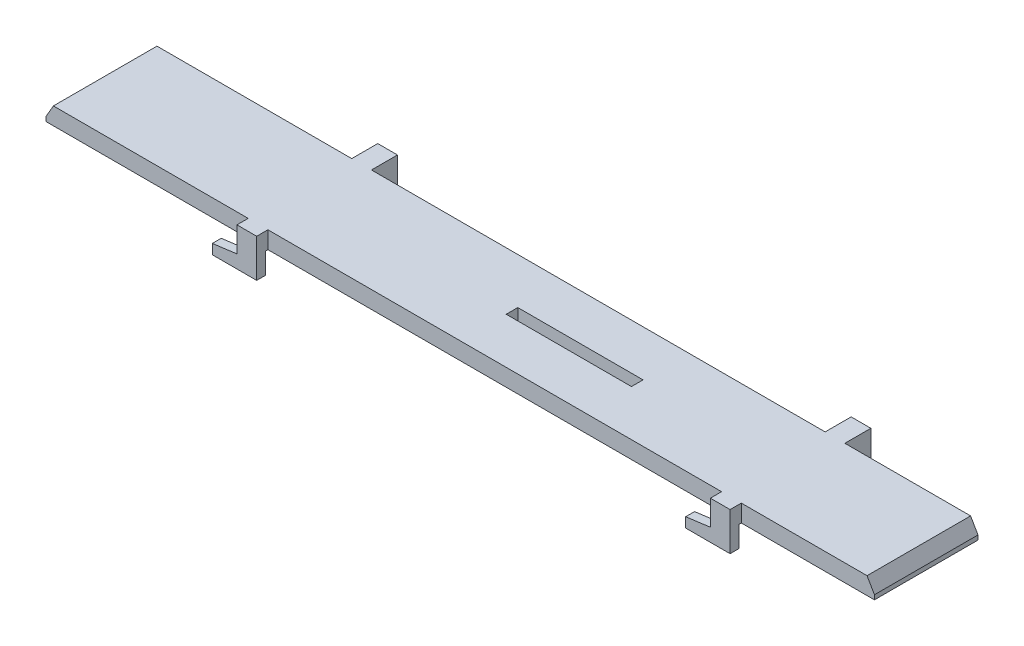
SolidWorks part; units mm, degrees
note: The reader was unsure of these and kept them because the rebuilt part matched: shared geometry of "Hook Sketch<2>".
ref_plane "Top" through (0, 0, 0) normal (0, 0, 1) x (1, 0, 0)
ref_plane "Front" through (0, 0, 0) normal (0, 1, 0) x (1, 0, 0)
ref_plane "Right" through (0, 0, 0) normal (1, 0, 0) x (0, 0, -1)
sketch "Top Sketch" plane through (0, 0, 0) normal (0, 1, 0) x (1, 0, 0)
  line L0 (-27, -11) -> (-27, -12.375)
  line L1 (-168, 10) -> (-127, 10)
  line L2 (-168, 10) -> (-168, -11)
  line L3 (-168, -11) -> (-127, -11)
  line L4 (0, 10) -> (0, -11)
  line L5 (-27, -12.375) -> (-36, -12.375) construction
  line L6 (-36, -12.375) -> (-36, -11) construction
  line L7 (-123, -11) -> (-123, -12.375)
  line L8 (-123, -12.375) -> (-132, -12.375) construction
  line L9 (-132, -12.375) -> (-132, -11) construction
  line L10 (-27, 10) -> (-27, 14.375)
  line L11 (-27, 14.375) -> (-36, 14.375) construction
  line L12 (-36, 14.375) -> (-36, 10) construction
  line L13 (-123, 10) -> (-123, 14.375)
  line L14 (-123, 14.375) -> (-132, 14.375) construction
  line L15 (-132, 14.375) -> (-132, 10) construction
  line L16 (-27, 10) -> (0, 10)
  line L17 (-27, -11) -> (0, -11)
  line L18 (-123, 10) -> (-31, 10)
  line L19 (-123, -11) -> (-31, -11)
  line L20 (-31, 14.375) -> (-31, 10)
  line L21 (-31, 14.375) -> (-27, 14.375)
  line L22 (-31, -11) -> (-31, -12.375)
  line L23 (-31, -12.375) -> (-27, -12.375)
  line L24 (-127, 14.375) -> (-127, 10)
  line L25 (-127, 14.375) -> (-123, 14.375)
  line L26 (-127, -12.375) -> (-127, -11)
  line L27 (-127, -12.375) -> (-123, -12.375)
  line L28 (-168, 0) -> (0, 0) construction
  point P32 (-84, 0)
  point P37 (0, -0.5)
  dimension "D1" = 4.375
  dimension "Width" = 21
  dimension "D2" = 1.375
  dimension "Length" = 168
  dimension "D3" = 0.5
  dimension "D5" = 5
  dimension "D8" = 4
extrude "Thickness Extrude" add sketch "Top Sketch" along normal blind 3.5
sketch "Hook Sketch" plane through (0, 0, 12.375) normal (0, 0, 1) x (1, 0, 0)
  line L0 (-31, 3.5) -> (-27, 3.5)
  line L1 (-31, 0) -> (-27, 0) construction
  line L2 (-27, 3.5) -> (-27, -4.2583)
  line L3 (-27, -4.2583) -> (-36, -4.2583)
  line L4 (-36, -4.2583) -> (-36, -2.2583)
  line L5 (-36, -2.2583) -> (-31, -1.6)
  line L6 (-31, -1.6) -> (-31, 3.5)
  dimension "D1" = 7.5
  dimension "D2" = 5
  dimension "D3" = 1.6
  dimension "D4" = 2
extrude "Hook 1 Extrude" add sketch "Hook Sketch" against normal blind 0.9 and the other way blind 0.9 separate body
extrude "Hook 2 Extrude" add sketch "Hook Sketch<2>" along normal blind 0.9 and the other way blind 0.9 from surface at -26.75 separate body
sketch "Hook Sketch<2>" plane through (0, 0, 12.375) normal (0, 0, 1) x (1, 0, 0) same geometry as "Hook Sketch"
pattern_linear "Hook Pattern" count 2 spacing 96 along (-1, 0, 0) of "Hook 1 Extrude", "Hook 2 Extrude"
combine bodies "Combine Bodies" operation type add bodies to combine 101 103 104 105 106
sketch "Handle Sketch" plane through (0, 3.5, 0) normal (0, 1, 0) x (1, 0, 0)
  line L1 (-168, -0.5) -> (0, -0.5) construction
  line L3 (-84, 0.675) -> (-58.6, 0.675)
  line L4 (-84, 0.675) -> (-84, -1.675)
  line L5 (-58.6, 0.675) -> (-58.6, -1.675)
  line L6 (-58.6, -1.675) -> (-84, -1.675)
  line L9 (-168, 10) -> (-168, -11) construction
  line L10 (0, -11) -> (0, 10) construction
  point P2 (-84, -0.5)
extrude "Handle Slot Cut" cut sketch "Handle Sketch" against normal blind 3
chamfer "Handle Slot Chamfer 1" distance 1.175 angle 67.5 1 edges at (-71.3, 0.5, 1.675)
chamfer "Handle Slot Chamfer 2" [suppressed] distance 1.175 angle 67.5
chamfer "End Chamfers" distance 2.6 angle 30 2 edges at (0, 3.5, 0.5) (-168, 3.5, 0.5)
equation "\"Handle Opening Width\"= 2.35"
equation "\"D1@Handle Sketch\"=\"Handle Opening Width\""
equation "\"D1@Handle Slot Chamfer 1\" = \"Handle Opening Width\" / 2"
equation "\"D1@Handle Slot Chamfer 2\" = \"Handle Opening Width\" / 2"
equation "\"Handle Chamfer Angle\"= 67.5deg"
equation "\"D2@Handle Slot Chamfer 1\"=\"Handle Chamfer Angle\""
equation "\"D2@Handle Slot Chamfer 2\"=\"Handle Chamfer Angle\""
